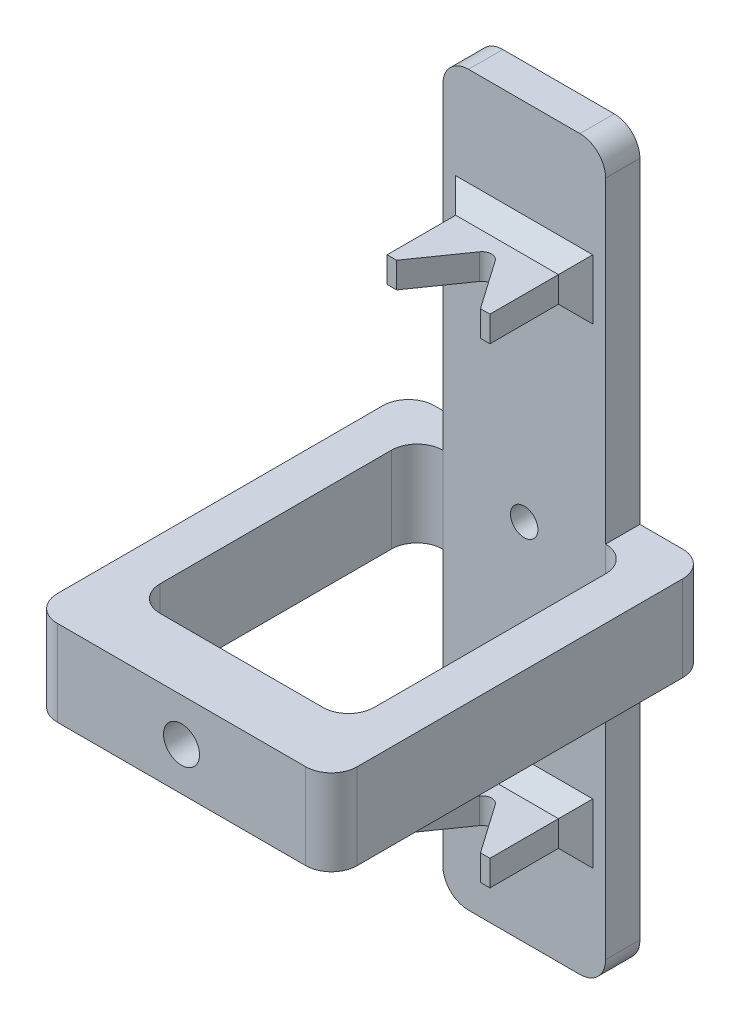
SolidWorks part; units mm, degrees
ref_plane "Front Plane" through (0, 0, 0) normal (0, 0, 1) x (1, 0, 0)
ref_plane "Top Plane" through (0, 0, 0) normal (0, 1, 0) x (1, 0, 0)
ref_plane "Right Plane" through (0, 0, 0) normal (1, 0, 0) x (0, 0, -1)
sketch "Sketch1" plane through (0, 0, 0) normal (0, 0, 1) x (1, 0, 0)
  line L1 (-7.5, 42.5) -> (7.5, 42.5)
  line L2 (-7.5, 42.5) -> (-7.5, -42.5)
  line L3 (-7.5, -42.5) -> (7.5, -42.5)
  line L4 (7.5, 42.5) -> (7.5, -42.5)
  line L5 (-7.5, 42.5) -> (7.5, -42.5) construction
  line L6 (-7.5, -42.5) -> (7.5, 42.5) construction
  point P0 (0, 0)
  dimension "D1" = 85
  dimension "D2" = 15
extrude "Boss-Extrude1" add sketch "Sketch1" along normal blind 4
sketch "Sketch2" plane through (0, 0, 4) normal (0, 0, 1) x (1, 0, 0)
  line L0 (0, 42.5) -> (0, 27.5)
  line L1 (0, -42.5) -> (0, -27.5)
  line L3 (-6, 29) -> (6, 29)
  line L4 (7.5, -42.5) -> (7.5, 42.5)
  line L5 (7.5, 42.5) -> (-7.5, 42.5)
  line L6 (-7.5, 42.5) -> (-7.5, -42.5)
  line L7 (-7.5, -42.5) -> (7.5, -42.5)
  line L9 (7.5, 42.5) -> (-7.5, 42.5)
  line L11 (-7.5, -42.5) -> (7.5, -42.5)
  line L12 (-6, 29) -> (-6, 26)
  line L13 (-6, 26) -> (6, 26)
  line L14 (6, 29) -> (6, 26)
  line L15 (-6, 29) -> (6, 26) construction
  line L16 (-6, 26) -> (6, 29) construction
  line L17 (-6, -29) -> (6, -29)
  line L18 (-6, -29) -> (-6, -26)
  line L19 (-6, -26) -> (6, -26)
  line L20 (6, -29) -> (6, -26)
  line L21 (-6, -29) -> (6, -26) construction
  line L22 (-6, -26) -> (6, -29) construction
  dimension "D2" = 15
  dimension "D3" = 15
  dimension "D4" = 3
  dimension "D5" = 12
  dimension "D6" = 3
  dimension "D7" = 12
  dimension "D1" = 0
extrude "Boss-Extrude2" add sketch "Sketch2" along normal blind 10 contours L14 L3 L12 L13 | L17 L20 L19 L18 region at (3, 28.8763, 4) region at (-3, -28.8763, 4)
sketch "Sketch3" plane through (0, 29, 0) normal (0, 1, 0) x (1, 0, 0)
  line L0 (0, -14) -> (0, -7)
  line L1 (-0.9046, -8.2934) -> (-4.896, -14)
  line L2 (0.9046, -8.2934) -> (4.896, -14)
  line L4 (6, -4) -> (-6, -4)
  line L5 (-6, -4) -> (-6, -14)
  line L6 (-6, -14) -> (6, -14)
  line L7 (6, -14) -> (6, -4)
  line L8 (6, -4) -> (-6, -4)
  line L9 (-6, -4) -> (-6, -12.896)
  line L10 (-4.896, -14) -> (4.896, -14)
  line L11 (6, -12.896) -> (6, -4)
  arc A0 (6, -12.896) -> (4.896, -14) centre (4.896, -12.896) cw
  arc A1 (-4.896, -14) -> (-6, -12.896) centre (-4.896, -12.896) cw
  arc A2 (0.9046, -8.2934) -> (-0.9046, -8.2934) centre (0, -8.9261) ccw
  line M9 (-6, -14) -> (6, -14)
  dimension "D2" = 1.104
  dimension "D4" = 1.104
  dimension "D3" = 7
  dimension "D1" = 0
extrude "Cut-Extrude1" cut sketch "Sketch3" against normal blind 60 contours L2 A2 L0 M9 | L0 A2 L1 M9 region at (-1.6555, 29, 11.7355) region at (1.6555, 29, 11.7355)
sketch "Sketch4" plane through (0, 0, 4) normal (0, 0, 1) x (1, 0, 0)
  line L0 (0, 0) -> (0, -15.4)
  circle A0 centre (0, -15.4) radius 1.6
  circle A1 centre (0, 0) radius 1.6
  dimension "D2" = 3.2
  dimension "D3" = 3.2
  dimension "D1" = 15.4
extrude "Cut-Extrude2" cut sketch "Sketch4" against normal blind 4 contours A1 | A0 region at (1.0994, -14.3006, 4) region at (-1.0994, 1.0994, 4)
sketch "Sketch5" plane through (0, 42.5, 0) normal (0, 1, 0) x (1, 0, 0)
  line L1 (7.5, 0) -> (17.5, 0)
  line L2 (7.5, 0) -> (7.5, -4)
  line L3 (7.5, -4) -> (17.5, -4)
  line L4 (17.5, 0) -> (17.5, -4)
  line L5 (-7.5, 0) -> (-17.5, 0)
  line L6 (-7.5, 0) -> (-7.5, -4)
  line L7 (-7.5, -4) -> (-17.5, -4)
  line L8 (-17.5, 0) -> (-17.5, -4)
  dimension "D1" = 10
  dimension "D2" = 10
  dimension "D3" = 4
  dimension "D4" = 4
extrude "Boss-Extrude3" add sketch "Sketch5" against normal blind 50
sketch "Sketch8" plane through (0, 0, 4) normal (0, 0, 1) x (1, 0, 0)
  line L1 (17.5, 42.5) -> (7.5, 42.5)
  line L2 (17.5, 42.5) -> (17.5, 2.5)
  line L3 (17.5, 2.5) -> (7.5, 2.5)
  line L4 (7.5, 42.5) -> (7.5, 2.5)
  line L5 (-17.5, 42.5) -> (-7.5, 42.5)
  line L6 (-17.5, 42.5) -> (-17.5, 2.5)
  line L7 (-17.5, 2.5) -> (-7.5, 2.5)
  line L8 (-7.5, 42.5) -> (-7.5, 2.5)
  dimension "D1" = 40
  dimension "D2" = 10
  dimension "D3" = 40
  dimension "D4" = 10
extrude "Cut-Extrude3" cut sketch "Sketch8" against normal blind 4
sketch "Sketch10" plane through (0, 0, 4) normal (0, 0, 1) x (1, 0, 0)
  line L1 (17.5, 2.5) -> (7.5, 2.5)
  line L2 (17.5, 2.5) -> (17.5, -7.5)
  line L3 (17.5, -7.5) -> (7.5, -7.5)
  line L4 (7.5, 2.5) -> (7.5, -7.5)
  line L5 (-17.5, 2.5) -> (-7.5, 2.5)
  line L6 (-17.5, 2.5) -> (-17.5, -7.5)
  line L7 (-17.5, -7.5) -> (-7.5, -7.5)
  line L8 (-7.5, 2.5) -> (-7.5, -7.5)
extrude "Boss-Extrude4" add sketch "Sketch10" along normal blind 40
sketch "Sketch11" plane through (7.5, 0, 0) normal (-1, 0, 0) x (0, 0, 1)
  line L1 (44, 2.5) -> (37, 2.5)
  line L2 (44, 2.5) -> (44, -7.5)
  line L3 (44, -7.5) -> (37, -7.5)
  line L4 (37, 2.5) -> (37, -7.5)
  dimension "D1" = 10
  dimension "D2" = 7
extrude "Boss-Extrude5" add sketch "Sketch11" along normal up to surface (15 mm away) up to face at (-7.5, -2.5, 24)
sketch "Sketch13" plane through (0, 2.5, 0) normal (0, 1, 0) x (1, 0, 0)
  line L3 (-7.5, -4) -> (-12.5, -4)
  line L4 (-7.5, -4) -> (-7.5, -37)
  line L5 (-7.5, -37) -> (-12.5, -37)
  line L6 (-12.5, -4) -> (-12.5, -37)
  line L7 (7.5, -4) -> (12.5, -4)
  line L8 (7.5, -4) -> (7.5, -37)
  line L9 (7.5, -37) -> (12.5, -37)
  line L10 (12.5, -4) -> (12.5, -37)
  dimension "D1" = 33
  dimension "D2" = 5
  dimension "D3" = 33
  dimension "D4" = 5
extrude "Cut-Extrude4" cut sketch "Sketch13" against normal blind 10
sketch "Sketch14" plane through (0, 0, 44) normal (0, 0, 1) x (1, 0, 0)
  line L0 (0, -7.5) -> (0, 2.5)
  line L1 (-17.5, -7.5) -> (17.5, -7.5) construction
  line L2 (17.5, 2.5) -> (-17.5, 2.5) construction
  circle A0 centre (0, -2.5) radius 2.1
  dimension "D1" = 4.2
extrude "Cut-Extrude6" cut sketch "Sketch14" against normal up to surface (7 mm away) contours L0 A0 | L0 A0 region at (-0.8913, -2.5, 44) region at (0.8913, -2.5, 44) up to face at (0, -2.5, 37)
sketch "Sketch17" plane through (7.5, 0, 0) normal (1, 0, 0) x (0, 0, -1)
  line L4 (0, -42.5) -> (0, -7.5)
  line L5 (0, -7.5) -> (-4, -7.5)
  line L6 (-4, -7.5) -> (-4, -42.5)
  line L7 (-4, -42.5) -> (0, -42.5)
  line L8 (0, -42.5) -> (0, -7.5)
  line L9 (0, -7.5) -> (-4, -7.5)
  line L10 (-4, -7.5) -> (-4, -42.5)
  line L11 (-4, -42.5) -> (0, -42.5)
  line L12 (-4, 42.5) -> (-4, 2.5)
  line L13 (-4, 2.5) -> (0, 2.5)
  line L14 (0, 2.5) -> (0, 42.5)
  line L15 (0, 42.5) -> (-4, 42.5)
  line L16 (-4, 42.5) -> (-4, 2.5)
  line L17 (-4, 2.5) -> (0, 2.5)
  line L18 (0, 2.5) -> (0, 42.5)
  line L19 (0, 42.5) -> (-4, 42.5)
  dimension "D1" = 0
  dimension "D2" = 0
extrude "Boss-Extrude6" add sketch "Sketch17" along normal blind 2
sketch "Sketch18" plane through (-7.5, 0, 0) normal (-1, 0, 0) x (0, 0, 1)
  line L4 (4, -42.5) -> (4, -7.5)
  line L5 (4, -7.5) -> (0, -7.5)
  line L6 (0, -7.5) -> (0, -42.5)
  line L7 (0, -42.5) -> (4, -42.5)
  line L8 (4, -42.5) -> (4, -7.5)
  line L10 (0, -7.5) -> (0, -42.5)
  line L11 (0, -42.5) -> (4, -42.5)
  line L12 (4, 2.5) -> (4, 42.5)
  line L13 (4, 42.5) -> (0, 42.5)
  line L14 (0, 42.5) -> (0, 2.5)
  line L15 (0, 2.5) -> (4, 2.5)
  line L16 (4, 2.5) -> (4, 42.5)
  line L17 (4, 42.5) -> (0, 42.5)
  line L18 (0, 42.5) -> (0, 2.5)
  line L19 (0, 2.5) -> (4, 2.5)
  line L21 (4, -7.5) -> (0, -7.5)
  dimension "D1" = 0
  dimension "D2" = 0
extrude "Boss-Extrude7" add sketch "Sketch18" along normal blind 2
fillet "Fillet2" radius 3 12 edges at (9.5, -42.5, 2) (-9.5, -42.5, 2) (9.5, 42.5, 2) (-9.5, 42.5, 2) (-17.5, -2.5, 0) (17.5, -2.5, 44) (-17.5, -2.5, 44) (12.5, -2.5, 37) (-12.5, -2.5, 37) (17.5, -2.5, 0) (12.5, -2.5, 4) (-12.5, -2.5, 4)
chamfer "Chamfer1" distance 2 angle 45 8 edges at (-6, -27.5, 4) (0, -26, 4) (6, -27.5, 4) (0, -29, 4) (0, 29, 4) (0, 26, 4) (-6, 27.5, 4) (6, 27.5, 4)
sketch "Sketch19" plane through (0, 0, 37) normal (0, 0, -1) x (-1, 0, 0)
  line L1 (4.1569, -2.5) -> (2.0785, 1.1)
  line L2 (2.0785, 1.1) -> (-2.0785, 1.1)
  line L3 (-2.0785, 1.1) -> (-4.1569, -2.5)
  line L4 (-4.1569, -2.5) -> (-2.0785, -6.1)
  line L5 (-2.0785, -6.1) -> (2.0785, -6.1)
  line L6 (2.0785, -6.1) -> (4.1569, -2.5)
  circle A0 centre (0, -2.5) radius 3.6 construction
  point P1 (0, 1.1)
  dimension "D1" = 7.2
extrude "Cut-Extrude7" cut sketch "Sketch19" against normal blind 3.5
